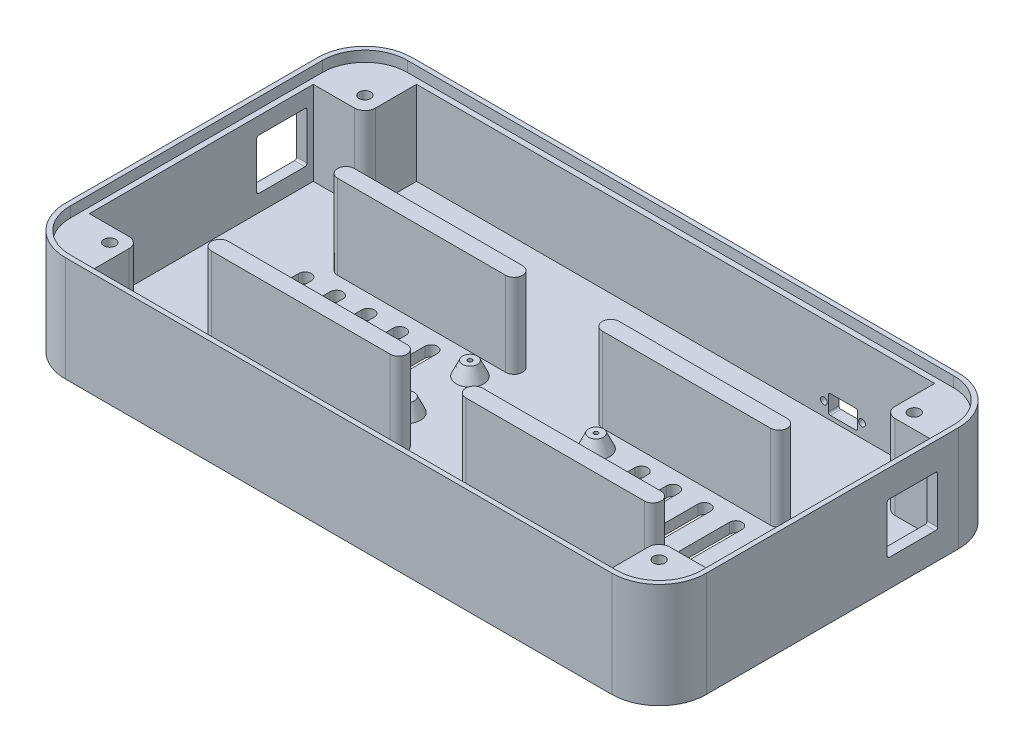
SolidWorks part; units mm, degrees
ref_plane "前视基准面" through (0, 0, 0) normal (0, 0, 1) x (1, 0, 0)
ref_plane "上视基准面" through (0, 0, 0) normal (0, 1, 0) x (1, 0, 0)
ref_plane "右视基准面" through (0, 0, 0) normal (1, 0, 0) x (0, 0, -1)
sketch "草图1" plane through (0, 0, 0) normal (0, 1, 0) x (1, 0, 0)
  line L1 (-152.5, 82.5) -> (152.5, 82.5)
  line L2 (-152.5, 82.5) -> (-152.5, -82.5)
  line L3 (-152.5, -82.5) -> (152.5, -82.5)
  line L4 (152.5, 82.5) -> (152.5, -82.5)
  line L5 (-152.5, 82.5) -> (152.5, -82.5) construction
  line L6 (-152.5, -82.5) -> (152.5, 82.5) construction
  point P0 (0, 0)
  dimension "D1" = 305
  dimension "D2" = 165
extrude "凸台-拉伸1" add sketch "草图1" along normal blind 50
fillet "圆角1" radius 22.5 4 edges at (-152.5, 25, -82.5) (-152.5, 25, 82.5) (152.5, 25, -82.5) (152.5, 25, 82.5)
shell "抽壳1" thickness 5 removed face at (0, 50, 0)
sketch "草图5" plane through (0, 50, 0) normal (0, 1, 0) x (1, 0, 0)
  line L0 (130, 80.2) -> (-130, 80.2)
  line L1 (-150.2, 60) -> (-150.2, -60)
  line L2 (-130, -80.2) -> (130, -80.2)
  line L3 (150.2, -60) -> (150.2, 60)
  line L4 (-147.5, 60) -> (-147.5, -60)
  line L5 (-130, -77.5) -> (130, -77.5)
  line L6 (147.5, -60) -> (147.5, 60)
  line L7 (130, 77.5) -> (-130, 77.5)
  line L8 (-147.5, 60) -> (-147.5, -60)
  line L9 (-130, -77.5) -> (130, -77.5)
  line L10 (147.5, -60) -> (147.5, 60)
  line L11 (130, 77.5) -> (-130, 77.5)
  arc A0 (-130, 80.2) -> (-150.2, 60) centre (-130, 60) ccw
  arc A1 (-150.2, -60) -> (-130, -80.2) centre (-130, -60) ccw
  arc A2 (130, -80.2) -> (150.2, -60) centre (130, -60) ccw
  arc A3 (150.2, 60) -> (130, 80.2) centre (130, 60) ccw
  arc A4 (-147.5, -60) -> (-130, -77.5) centre (-130, -60) ccw
  arc A5 (130, -77.5) -> (147.5, -60) centre (130, -60) ccw
  arc A6 (147.5, 60) -> (130, 77.5) centre (130, 60) ccw
  arc A7 (-130, 77.5) -> (-147.5, 60) centre (-130, 60) ccw
  arc A8 (-147.5, -60) -> (-130, -77.5) centre (-130, -60) ccw
  arc A9 (130, -77.5) -> (147.5, -60) centre (130, -60) ccw
  arc A10 (147.5, 60) -> (130, 77.5) centre (130, 60) ccw
  arc A11 (-130, 77.5) -> (-147.5, 60) centre (-130, 60) ccw
  dimension "D1" = 0
  dimension "D2" = 2.7
extrude "切除-拉伸1" cut sketch "草图5" against normal blind 5
sketch "草图6" plane through (0, 5, 0) normal (0, 1, 0) x (1, 0, 0)
  line L0 (-147.5, 60) -> (-130, 60) construction
  line L1 (-130, 60) -> (-130, 77.5) construction
  line L2 (-130, 60) -> (-142.3744, 72.3744) construction
  line L3 (-147.5, 52.9289) -> (-122.9289, 52.9289)
  line L4 (-147.5, 60) -> (-147.5, -60)
  line L5 (-130, -77.5) -> (130, -77.5)
  line L6 (147.5, -60) -> (147.5, 60)
  line L7 (130, 77.5) -> (-130, 77.5)
  line L8 (-147.5, 60) -> (-147.5, -60)
  line L9 (-130, -77.5) -> (130, -77.5)
  line L10 (147.5, -60) -> (147.5, 60)
  line L11 (130, 77.5) -> (-130, 77.5)
  line L12 (-122.9289, 52.9289) -> (-122.9289, 77.5)
  line L13 (-130, 60) -> (-122.9289, 52.9289) construction
  line L14 (130, 77.5) -> (130, 60) construction
  line L15 (130, 60) -> (147.5, 60) construction
  line L16 (130, 60) -> (142.3744, 72.3744) construction
  line L17 (123.636, 77.5) -> (123.636, 53.636)
  line L18 (123.636, 53.636) -> (147.5, 53.636)
  line L19 (123.636, 53.636) -> (130.7071, 60.7071) construction
  line L20 (-147.5, -60) -> (-130, -60) construction
  line L21 (-130, -60) -> (-130, -77.5) construction
  line L22 (-130, -60) -> (-142.3744, -72.3744) construction
  line L23 (-123.636, -77.5) -> (-123.636, -53.636)
  line L24 (-123.636, -53.636) -> (-147.5, -53.636)
  line L25 (-130.7071, -60.7071) -> (-123.636, -53.636) construction
  line L26 (147.5, -60) -> (130, -60) construction
  line L27 (130, -60) -> (130, -77.5) construction
  line L28 (130, -60) -> (142.3744, -72.3744) construction
  line L29 (130, -60) -> (122.9289, -52.9289) construction
  line L30 (122.9289, -52.9289) -> (147.5, -52.9289)
  line L31 (122.9289, -52.9289) -> (122.9289, -77.5)
  circle A0 centre (-130.7071, 60.7071) radius 2.75
  circle A1 centre (130.7071, 60.7071) radius 2.75
  circle A2 centre (-130.7071, -60.7071) radius 2.75
  circle A3 centre (130.7071, -60.7071) radius 2.75
  arc A4 (-147.5, -60) -> (-130, -77.5) centre (-130, -60) ccw
  arc A5 (130, -77.5) -> (147.5, -60) centre (130, -60) ccw
  arc A6 (147.5, 60) -> (130, 77.5) centre (130, 60) ccw
  arc A7 (-130, 77.5) -> (-147.5, 60) centre (-130, 60) ccw
  arc A8 (-147.5, -60) -> (-130, -77.5) centre (-130, -60) ccw
  arc A9 (130, -77.5) -> (147.5, -60) centre (130, -60) ccw
  arc A10 (147.5, 60) -> (130, 77.5) centre (130, 60) ccw
  arc A11 (-130, 77.5) -> (-147.5, 60) centre (-130, 60) ccw
  line M13 (-147.5, 60) -> (-147.5, -60)
  arc M14 (-147.5, -60) -> (-130, -77.5) centre (-130, -60) ccw
  line M15 (-130, -77.5) -> (130, -77.5)
  arc M16 (130, -77.5) -> (147.5, -60) centre (130, -60) ccw
  line M17 (147.5, -60) -> (147.5, 60)
  arc M18 (147.5, 60) -> (130, 77.5) centre (130, 60) ccw
  line M19 (130, 77.5) -> (-130, 77.5)
  arc M20 (-130, 77.5) -> (-147.5, 60) centre (-130, 60) ccw
  dimension "D4" = 5.5
  dimension "D7" = 5.5
  dimension "D10" = 5.5
  dimension "D13" = 5.5
  dimension "D2" = 17.5
  dimension "D3" = 1
  dimension "D5" = 10
  dimension "D6" = 1
  dimension "D8" = 10
  dimension "D9" = 1
  dimension "D11" = 10
  dimension "D12" = 1
  dimension "D14" = 10
  dimension "D1" = 0
extrude "凸台-拉伸3" add sketch "草图6" along normal up to surface (40 mm away) contours L17 L18 L10 A1 M18 M19 | L30 L31 A3 M15 M16 M17 | L23 L24 L8 A2 M14 M15 | L3 L12 L11 A0 M20 M13 region at (-134.3522, 5, -64.3522) region at (-134.7101, 5, 64.7101) region at (134.7101, 5, -64.7101) region at (134.3522, 5, 64.3522) up to face at (0, 45, 0)
fillet "圆角2" radius 5 4 edges at (-123.636, 25, 53.636) (122.9289, 25, 52.9289) (123.636, 25, -53.636) (-122.9289, 25, -52.9289)
sketch "草图7" plane through (-152.5, 0, 0) normal (-1, 0, 0) x (0, 0, 1)
  line L0 (-60, 50) -> (-60, 0) construction
  line L1 (-50, 37) -> (-26, 37)
  line L2 (-50, 37) -> (-50, 13)
  line L3 (-50, 13) -> (-26, 13)
  line L4 (-26, 37) -> (-26, 13)
  line L5 (-60, 0) -> (60, 0) construction
  point P6 (-26, 25)
  dimension "D1" = 24
  dimension "D2" = 10
  dimension "D3" = 25
extrude "切除-拉伸2" cut sketch "草图7" against normal through all both and the other way through all
sketch "草图8" plane through (0, 0, -82.5) normal (0, 0, -1) x (-1, 0, 0)
  line L0 (-89.1, 11.5) -> (-70.9, 11.5) construction
  line L1 (-87, 16) -> (-73, 16)
  line L2 (-87, 16) -> (-87, 7)
  line L3 (-87, 7) -> (-73, 7)
  line L4 (-73, 16) -> (-73, 7)
  line L5 (-87, 16) -> (-73, 7) construction
  line L6 (-87, 7) -> (-73, 16) construction
  line L7 (-130, 50) -> (-130, 0) construction
  line L8 (-130, 0) -> (130, 0) construction
  circle A0 centre (-89.1, 11.5) radius 1.6
  circle A1 centre (-70.9, 11.5) radius 1.6
  point P0 (-80, 11.5)
  point P7 (-80, 11.5)
  dimension "D2" = 3.2
  dimension "D3" = 3.2
  dimension "D1" = 9.1
  dimension "D4" = 14
  dimension "D5" = 9
  dimension "D6" = 50
  dimension "D7" = 7
extrude "切除-拉伸3" cut sketch "草图8" against normal blind 5
sketch "草图9" plane through (0, 5, 0) normal (0, 1, 0) x (1, 0, 0)
  line L0 (0, 0) -> (50000, 0) construction
  line L1 (0, 0) -> (0, -50000) construction
  line L2 (-103, 24) -> (-23, 24) construction
  line L3 (-103, 28) -> (-23, 28)
  line L4 (-103, 20) -> (-23, 20)
  line L5 (103, 24) -> (23, 24) construction
  line L6 (103, 28) -> (23, 28)
  line L7 (103, 20) -> (23, 20)
  line L8 (-103, -36) -> (-18, -36) construction
  line L9 (-103, -32) -> (-18, -32)
  line L10 (-103, -40) -> (-18, -40)
  line L11 (103, -36) -> (18, -36) construction
  line L12 (103, -32) -> (18, -32)
  line L13 (103, -40) -> (18, -40)
  arc A0 (-103, 28) -> (-103, 20) centre (-103, 24) ccw
  arc A1 (-23, 20) -> (-23, 28) centre (-23, 24) ccw
  arc A2 (103, 28) -> (103, 20) centre (103, 24) cw
  arc A3 (23, 20) -> (23, 28) centre (23, 24) cw
  arc A4 (-103, -32) -> (-103, -40) centre (-103, -36) ccw
  arc A5 (-18, -40) -> (-18, -32) centre (-18, -36) ccw
  arc A6 (103, -32) -> (103, -40) centre (103, -36) cw
  arc A7 (18, -40) -> (18, -32) centre (18, -36) cw
  point P7 (-63, 24)
  point P15 (63, 24)
  point P20 (-60.5, -36)
  point P28 (60.5, -36)
  dimension "D3" = 4
  dimension "D7" = 4
  dimension "D1" = 80
  dimension "D2" = 23
  dimension "D4" = 20
  dimension "D5" = 18
  dimension "D6" = 85
  dimension "D8" = 32
extrude "凸台-拉伸4" add sketch "草图9" along normal up to surface (40 mm away) up to face at (0, 45, 0)
sketch "草图10" plane through (0, 5, 0) normal (0, 1, 0) x (1, 0, 0)
  line L0 (0, 0) -> (50000, 0) construction
  line L1 (-30, 10) -> (30, 10) construction
  line L2 (-30, 10) -> (-30, -20) construction
  line L3 (-30, -20) -> (30, -20) construction
  line L4 (30, 10) -> (30, -20) construction
  line L5 (-30, 10) -> (30, -20) construction
  line L6 (-30, -20) -> (30, 10) construction
  line L7 (0, 0) -> (0, -50000) construction
  line L8 (-30, -5) -> (30, -5) construction
  circle A0 centre (-30, 10) radius 1
  circle A1 centre (30, 10) radius 1
  circle A2 centre (30, -20) radius 1
  circle A3 centre (-30, -20) radius 1
  circle A4 centre (-30, -20) radius 3.5
  circle A5 centre (-30, 10) radius 3.5
  circle A6 centre (30, 10) radius 3.5
  circle A7 centre (30, -20) radius 3.5
  point P0 (0, -5)
  dimension "D4" = 2
  dimension "D5" = 2
  dimension "D6" = 2
  dimension "D7" = 2
  dimension "D1" = 60
  dimension "D2" = 30
  dimension "D3" = 5
  dimension "D8" = 2.5
extrude "凸台-拉伸5" add sketch "草图10" along normal blind 6.5
sketch "草图11" plane through (0, 5, 0) normal (0, 1, 0) x (1, 0, 0)
  circle A0 centre (30, 10) radius 1 construction
  circle A1 centre (30, -20) radius 1 construction
  circle A2 centre (-30, -20) radius 1 construction
  circle A3 centre (-30, 10) radius 1 construction
  circle A4 centre (30, 10) radius 1
  circle A5 centre (30, -20) radius 1
  circle A6 centre (-30, -20) radius 1
  circle A7 centre (-30, 10) radius 1
extrude "切除-拉伸4" cut sketch "草图11" against normal blind 2.5
sketch "草图12" plane through (0, 5, 0) normal (0, 1, 0) x (1, 0, 0)
  line L0 (0, 0) -> (50000, 0) construction
  line L1 (0, 0) -> (0, -50000) construction
  line L2 (-110, 11.5) -> (-110, -23.5) construction
  line L3 (-107, 11.5) -> (-107, -23.5)
  line L4 (-113, 11.5) -> (-113, -23.5)
  line L5 (-95, 11.5) -> (-95, -23.5) construction
  line L6 (-92, 11.5) -> (-92, -23.5)
  line L7 (-98, 11.5) -> (-98, -23.5)
  line L8 (-80, 11.5) -> (-80, -23.5) construction
  line L9 (-77, 11.5) -> (-77, -23.5)
  line L10 (-83, 11.5) -> (-83, -23.5)
  line L11 (-65, 11.5) -> (-65, -23.5) construction
  line L12 (-62, 11.5) -> (-62, -23.5)
  line L13 (-68, 11.5) -> (-68, -23.5)
  line L14 (-50, 11.5) -> (-50, -23.5) construction
  line L15 (-47, 11.5) -> (-47, -23.5)
  line L16 (-53, 11.5) -> (-53, -23.5)
  line L17 (-110, 11.5) -> (-95, 11.5) construction
  line L18 (110, 11.5) -> (110, -23.5) construction
  line L19 (107, 11.5) -> (107, -23.5)
  line L20 (113, 11.5) -> (113, -23.5)
  line L21 (95, 11.5) -> (95, -23.5) construction
  line L22 (92, 11.5) -> (92, -23.5)
  line L23 (98, 11.5) -> (98, -23.5)
  line L24 (80, 11.5) -> (80, -23.5) construction
  line L25 (77, 11.5) -> (77, -23.5)
  line L26 (83, 11.5) -> (83, -23.5)
  line L27 (65, 11.5) -> (65, -23.5) construction
  line L28 (62, 11.5) -> (62, -23.5)
  line L29 (68, 11.5) -> (68, -23.5)
  line L30 (50, 11.5) -> (50, -23.5) construction
  line L31 (47, 11.5) -> (47, -23.5)
  line L32 (53, 11.5) -> (53, -23.5)
  arc A0 (-107, 11.5) -> (-113, 11.5) centre (-110, 11.5) ccw
  arc A1 (-113, -23.5) -> (-107, -23.5) centre (-110, -23.5) ccw
  arc A2 (-92, 11.5) -> (-98, 11.5) centre (-95, 11.5) ccw
  arc A3 (-98, -23.5) -> (-92, -23.5) centre (-95, -23.5) ccw
  arc A4 (-77, 11.5) -> (-83, 11.5) centre (-80, 11.5) ccw
  arc A5 (-83, -23.5) -> (-77, -23.5) centre (-80, -23.5) ccw
  arc A6 (-62, 11.5) -> (-68, 11.5) centre (-65, 11.5) ccw
  arc A7 (-68, -23.5) -> (-62, -23.5) centre (-65, -23.5) ccw
  arc A8 (-47, 11.5) -> (-53, 11.5) centre (-50, 11.5) ccw
  arc A9 (-53, -23.5) -> (-47, -23.5) centre (-50, -23.5) ccw
  arc A10 (107, 11.5) -> (113, 11.5) centre (110, 11.5) cw
  arc A11 (113, -23.5) -> (107, -23.5) centre (110, -23.5) cw
  arc A12 (92, 11.5) -> (98, 11.5) centre (95, 11.5) cw
  arc A13 (98, -23.5) -> (92, -23.5) centre (95, -23.5) cw
  arc A14 (77, 11.5) -> (83, 11.5) centre (80, 11.5) cw
  arc A15 (83, -23.5) -> (77, -23.5) centre (80, -23.5) cw
  arc A16 (62, 11.5) -> (68, 11.5) centre (65, 11.5) cw
  arc A17 (68, -23.5) -> (62, -23.5) centre (65, -23.5) cw
  arc A18 (47, 11.5) -> (53, 11.5) centre (50, 11.5) cw
  arc A19 (53, -23.5) -> (47, -23.5) centre (50, -23.5) cw
  point P7 (-110, -6)
  point P15 (-95, -6)
  point P22 (-80, -6)
  point P29 (-65, -6)
  point P36 (-50, -6)
  point P44 (110, -6)
  point P51 (95, -6)
  point P58 (80, -6)
  point P65 (65, -6)
  point P72 (50, -6)
  dimension "D1" = 3
  dimension "D2" = 110
  dimension "D3" = 6
  dimension "D4" = 35
  dimension "D6" = 15
  dimension "D5" = 5
extrude "切除-拉伸5" cut sketch "草图12" against normal up to next
sketch "草图13" plane through (0, 5, 0) normal (0, 1, 0) x (1, 0, 0)
  line L0 (-17.5, 62.45) -> (17.5, 62.45) construction
  line L1 (0, 50.95) -> (0, 62.45) construction
  line L2 (0, 0) -> (0, 50.95) construction
  line L3 (123.636, 77.5) -> (-122.9289, 77.5) construction
  circle A0 centre (-17.5, 62.45) radius 1.6
  circle A1 centre (17.5, 62.45) radius 1.6
  circle A2 centre (0, 50.95) radius 1.6
  point P8 (0, 0)
  dimension "D3" = 3.2
  dimension "D4" = 3.2
  dimension "D5" = 3.2
  dimension "D1" = 17.5
  dimension "D2" = 11.5
  dimension "D6" = 26.55
extrude "切除-拉伸6" cut sketch "草图13" against normal up to next
hole_wizard "M3 平头机械螺钉的锥形沉头孔1" positions "草图14" profile "草图15" countersink size "M3" standard "ANSI Metric"
sketch "草图14" plane through (0, 0, 0) normal (0, -1, 0) x (-1, 0, 0)
  point P0 (-17.5, 62.45)
  point P3 (0, 50.95)
  point P6 (17.5, 62.45)
sketch "草图15" plane through (17.5, 0, -62.45) normal (1, 0, 0) x (0, 0, -1)
  line L0 (0, 0) -> (0, 11.0815)
  line L1 (0, 11.0815) -> (1.8, 10)
  line L2 (1.8, 10) -> (1.8, 1.6)
  line L3 (1.8, 1.6) -> (3.4, 0)
  line L5 (3.4, 0) -> (0, 0)
  line L6 (-1.8, 1.6) -> (-3.4, 0) construction
  line L10 (0, 11.0815) -> (-1.8, 10) construction
  line L11 (0, -6.35) -> (0, 107.95) construction
  dimension "孔直径" = 3.6
  dimension "孔深度" = 10
  dimension "近端锥形沉头孔直径" = 6.8
  dimension "近端锥形沉头孔角度" = 90
  dimension "导头角度" = 118
chamfer "倒角2" distance 3 distance2 6.5 4 edges at (30, 5, -6.5) (30, 5, 23.5) (-30, 5, 23.5) (-30, 5, -6.5) first distance on face at (17.5, 5, -60.65)
fillet "圆角3" radius 1 4 edges at (73, 16, -80) (73, 7, -80) (87, 7, -80) (87, 16, -80)
fillet "圆角4" radius 1 8 edges at (150, 13, -50) (150, 13, -26) (150, 37, -26) (150, 37, -50) (-150, 37, -26) (-150, 13, -26) (-150, 13, -50) (-150, 37, -50)
